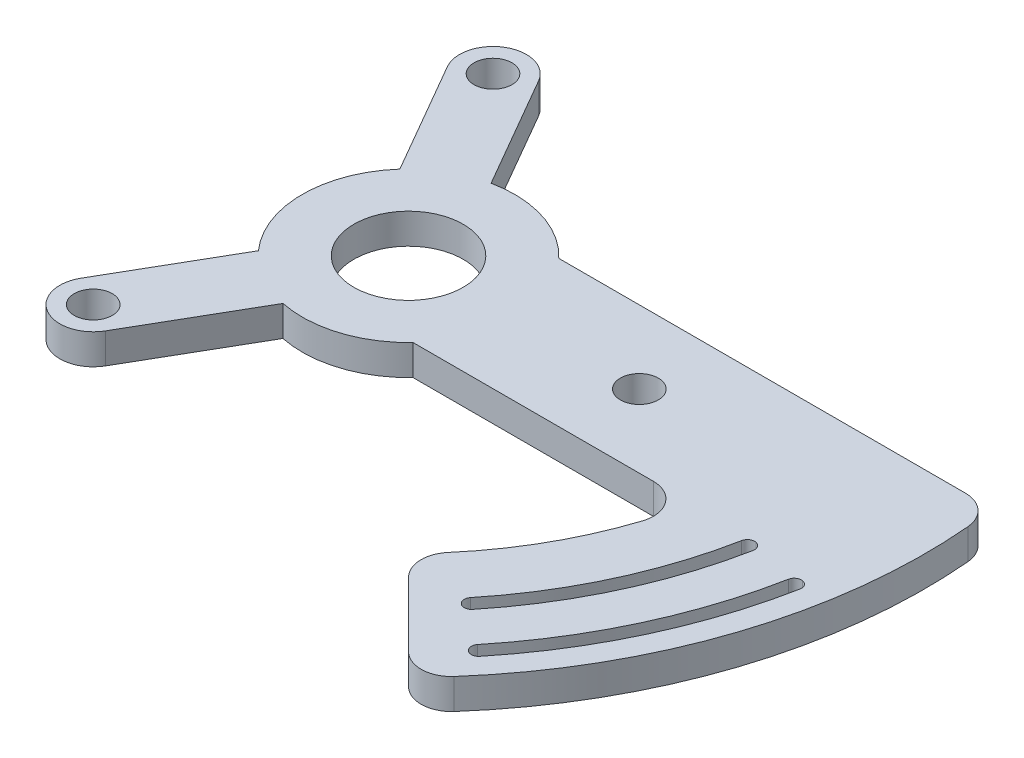
SolidWorks part; units mm, degrees
ref_plane "Front Plane" through (0, 0, 0) normal (0, 0, 1) x (1, 0, 0)
ref_plane "Top Plane" through (0, 0, 0) normal (0, 1, 0) x (1, 0, 0)
ref_plane "Right Plane" through (0, 0, 0) normal (1, 0, 0) x (0, 0, -1)
sketch "Sketch1" plane through (0, 0, 0) normal (0, 1, 0) x (1, 0, 0)
  circle A0 centre (0, 0) radius 9
  circle A1 centre (0, 0) radius 17.5
  dimension "D1" = 18
  dimension "D2" = 35
extrude "Boss-Extrude1" add sketch "Sketch1" along normal blind 5
sketch "Sketch3" plane through (0, 0, 0) normal (0, 1, 0) x (1, 0, 0)
  line L0 (0, 0) -> (38, 0) construction
  line L1 (10.0099, 5.5) -> (38, 5.5)
  line L2 (10.0099, 5.5) -> (10.0099, -5.5)
  line L3 (38, 5.5) -> (38, -5.5)
  line L4 (10.0099, -5.5) -> (38, -5.5)
  line L5 (38, 0) -> (10.0099, 0) construction
  line L6 (24.005, 5.5) -> (24.005, -5.5) construction
  circle A0 centre (0, 0) radius 38 construction
  circle A1 centre (38, 0) radius 5.5
  point P6 (24.005, 0)
  dimension "D1" = 76
  dimension "D2" = 11
  dimension "D3" = 11
extrude "Boss-Extrude3" add sketch "Sketch3" along normal up to surface (5 mm away) contours A1 L1 L2 L4 | L3 A1 | L3 A1 region at (21.8769, 0, 0) region at (40.3343, 0, 0) region at (35.6657, 0, 0) up to face at (0, 5, 17.5)
sketch "Sketch6" plane through (0, 0, 0) normal (0, 1, 0) x (1, 0, 0)
  line L0 (0, 0) -> (36.3689, 0) construction
  line L7 (60, -12) -> (12.7377, -12)
  line L8 (60, -12) -> (60, 12)
  line L9 (60, 12) -> (12.7377, 12)
  line L10 (12.7377, -12) -> (12.7377, 12)
  line L11 (36.3689, 12) -> (36.3689, -12) construction
  line L12 (60, 0) -> (12.7377, 0) construction
  arc A0 (16.6132, 5.5) -> (16.6132, -5.5) centre (0, 0) ccw construction
  circle A1 centre (0, 0) radius 9 construction
  point P6 (0, 0)
  dimension "D1" = 24
  dimension "D2" = 60
extrude "Boss-Extrude4" add sketch "Sketch6" along normal up to surface (5 mm away) up to face at (20.1533, 5, 0)
sketch "Sketch4" plane through (0, 5, 0) normal (0, 1, 0) x (1, 0, 0)
  line L0 (0, 0) -> (38, 0) construction
  circle A0 centre (38, 0) radius 3.125
  dimension "D1" = 6.25
  dimension "D2" = 38
extrude "Cut-Extrude1" cut sketch "Sketch4" against normal through all both and the other way through all
pattern_circular "CirPattern1" count 3 over 360 about axis through (0, 5, 0) along (0, 1, 0) of "Boss-Extrude3", "Cut-Extrude1"
sketch "Sketch7" plane through (0, 0, 0) normal (0, 1, 0) x (1, 0, 0)
  line L0 (0, 0) -> (93.8376, 0) construction
  line L1 (60, -12) -> (60, 12) construction
  line L2 (231.5477, -30) -> (-43.8724, -30) construction
  line L3 (231.5477, -30) -> (231.5477, 30) construction
  line L4 (231.5477, 30) -> (-43.8724, 30) construction
  line L5 (-43.8724, -30) -> (-43.8724, 30) construction
  line L6 (93.8376, 30) -> (93.8376, -30) construction
  line L7 (231.5477, 0) -> (-43.8724, 0) construction
  line L9 (42.4264, -42.4264) -> (60.1041, -60.1041)
  line L11 (60, 12) -> (12.7377, 12) construction
  line L12 (58.7878, 12) -> (84.1487, 12)
  arc A0 (85, 0) -> (60.1041, -60.1041) centre (0, 0) cw
  arc A1 (60, 0) -> (42.4264, -42.4264) centre (0, 0) cw
  arc A2 (85, 0) -> (84.1487, 12) centre (0, 0) ccw
  arc A3 (60, 0) -> (58.7878, 12) centre (0, 0) ccw
  point P13 (104.3121, 12)
  point P17 (0, 0)
  point P19 (105, 12)
  dimension "D1" = 60
  dimension "D2" = 25
  dimension "D3" = 45
extrude "Boss-Extrude5" add sketch "Sketch7" along normal up to surface (5 mm away) up to face at (-19, 5, -29.784)
sketch "Sketch8" plane through (0, 5, 0) normal (0, 1, 0) x (1, 0, 0)
  line L0 (0, 0) -> (85, 0) construction
  line L1 (69.4289, -12.2422) -> (78.7846, -13.8919) construction
  line L2 (61.2836, -51.423) -> (54.0061, -45.3165) construction
  arc A0 (60.1041, -60.1041) -> (84.1487, 12) centre (0, 0) ccw construction
  arc A1 (78.7846, -13.8919) -> (61.2836, -51.423) centre (0, 0) cw
  arc A2 (69.4289, -12.2422) -> (54.0061, -45.3165) centre (0, 0) cw
  point P11 (0, 0)
  point P12 (97.5764, 21.8825)
  point P13 (98.1308, 21.9844)
  point P14 (99.536, -9.6217)
  dimension "D1" = 5
  dimension "D2" = 9.5
  dimension "D3" = 10
  dimension "D4" = 40
extrude "Cut-Extrude-Thin1" cut sketch "Sketch8" against normal blind 10 thin thin type mid plane wall 2.4
fillet "Fillet1" radius 1.2 8 edges at (70.6107, 2.5, 12.4506) (79.9664, 2.5, 14.1002) (77.6029, 2.5, 13.6835) (68.2472, 2.5, 12.0338) (62.2028, 2.5, 52.1944) (60.3643, 2.5, 50.6517) (54.9254, 2.5, 46.0879) (53.0869, 2.5, 44.5452)
fillet "Fillet2" radius 5 4 edges at (84.1487, 2.5, -12) (60.1041, 2.5, 60.1041) (42.4264, 2.5, 42.4264) (58.7878, 2.5, 12)
